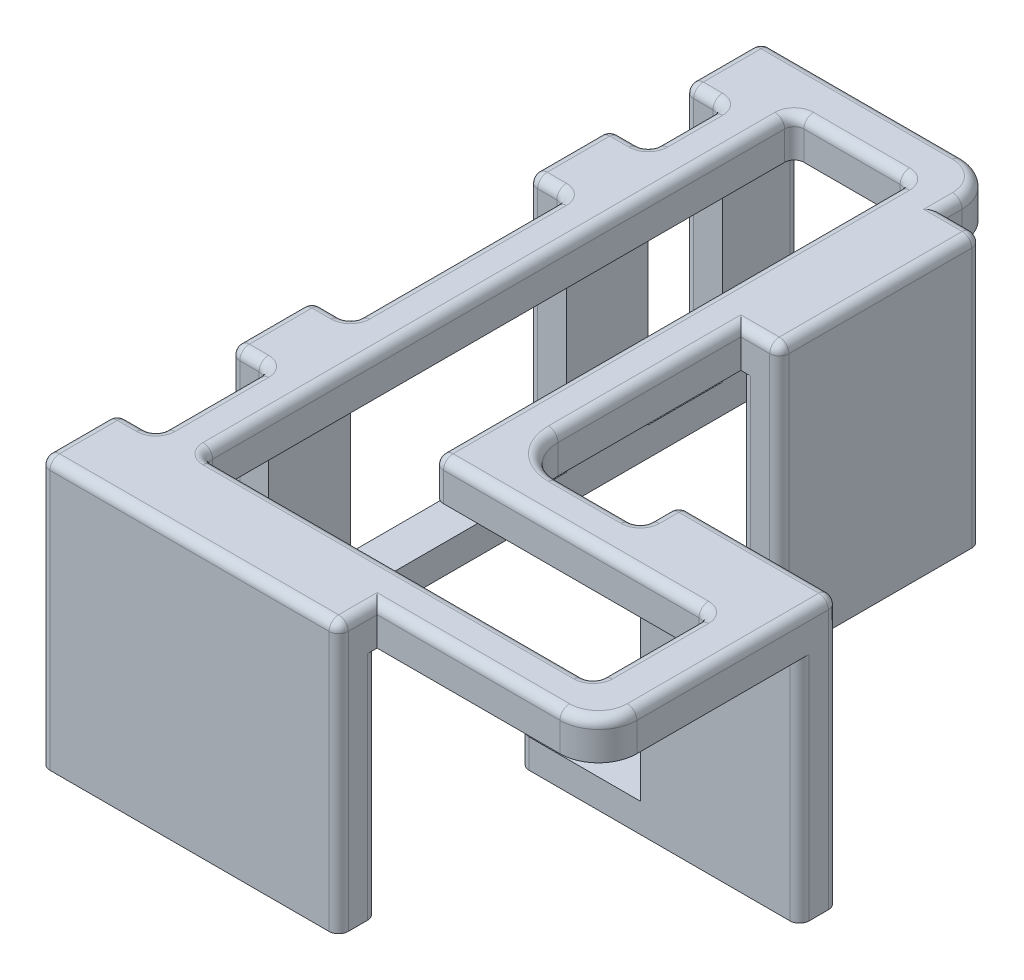
SolidWorks part; units mm, degrees
ref_plane "Front Plane" through (0, 0, 0) normal (0, 0, 1) x (1, 0, 0)
ref_plane "Top Plane" through (0, 0, 0) normal (0, 1, 0) x (1, 0, 0)
ref_plane "Right Plane" through (0, 0, 0) normal (1, 0, 0) x (0, 0, -1)
sketch "Sketch1" plane through (0, 0, 0) normal (0, 1, 0) x (1, 0, 0)
  line L5 (20.9, 20.9) -> (33.45, 20.9)
  line L6 (20.9, 43.9) -> (20.9, 20.9)
  line L18 (0, 46.675) -> (0, 35.45)
  line L23 (27, 0) -> (50, 0)
  line L27 (24.9, 43.9) -> (20.9, 43.9)
  line L30 (27, -4) -> (27, 0)
  line L42 (33.45, 24.9) -> (33.45, 20.9)
  line L43 (0, 24.225) -> (0, 35.45)
  line L51 (33.45, 24.9) -> (50, 24.9)
  line L52 (20.9, 70.9) -> (20.9, 64.9)
  line L53 (20.9, 64.9) -> (24.9, 64.9)
  line L54 (-4, 70.9) -> (20.9, 70.9)
  line L55 (24.9, 43.9) -> (24.9, 64.9)
  line L56 (-4, 51.175) -> (-4, 70.9)
  line L57 (-4, -4) -> (27, -4)
  line L58 (-4, -4) -> (-4, 19.725)
  line L59 (50, 0) -> (50, 24.9)
  line L60 (-4, 19.725) -> (-4, 24.225)
  line L61 (-4, 24.225) -> (0, 24.225)
  line L62 (-4, 51.175) -> (-4, 46.675)
  line L63 (-4, 46.675) -> (0, 46.675)
extrude "Boss-Extrude1" add sketch "Sketch1" along normal blind 4
sketch "Sketch2" plane through (0, 0, 0) normal (0, -1, 0) x (1, 0, 0)
  line L0 (27, 0) -> (23, 0)
  line L2 (23, 4) -> (27, 4)
  line L3 (27, 4) -> (27, 0)
  line L7 (33.45, -24.9) -> (33.45, -20.9)
  line L11 (24.9, -43.9) -> (20.9, -43.9)
  line L15 (-4, -15.725) -> (0, -15.725)
  line L17 (0, -55.175) -> (-4, -55.175)
  line L24 (23, 4) -> (-4, 4)
  line L25 (-4, 4) -> (-4, -4)
  line L26 (-4, -19.725) -> (-4, 4) construction
  line L27 (-4, -4) -> (0, -4)
  line L28 (0, -4) -> (0, 0)
  line L29 (0, 0) -> (23, 0)
  line L30 (33.45, -20.9) -> (50, -20.9)
  line L31 (50, 0) -> (50, -24.9) construction
  line L32 (50, -20.9) -> (50, -24.9)
  line L33 (50, -24.9) -> (33.45, -24.9)
  line L34 (-4, -70.9) -> (-4, -62.9)
  line L35 (-4, -70.9) -> (-4, -51.175) construction
  line L36 (-4, -62.9) -> (0, -62.9)
  line L37 (0, -62.9) -> (0, -70.9)
  line L38 (24.9, -70.9) -> (-4, -70.9) construction
  line L39 (0, -70.9) -> (-4, -70.9)
  line L43 (20.9, -43.9) -> (20.9, -64.9)
  line L44 (20.9, -64.9) -> (24.9, -64.9)
  line L45 (24.9, -64.9) -> (24.9, -43.9)
  line L46 (0, -15.725) -> (0, -24.225)
  line L47 (0, -24.225) -> (-4, -24.225)
  line L48 (-4, -24.225) -> (-4, -15.725)
  line L49 (0, -46.675) -> (0, -55.175)
  line L50 (0, -46.675) -> (-4, -46.675)
  line L51 (-4, -46.675) -> (-4, -55.175)
extrude "Boss-Extrude2" add sketch "Sketch2" along normal blind 24
fillet "Fillet2" radius 4 3 edges at (20.9, 2, -20.9) (20.9, 2, -70.9) (50, 2, 0)
sketch "Sketch5" plane through (0, -24, 0) normal (0, -1, 0) x (-1, 0, 0)
  line L0 (0, 19.725) -> (0, 0)
  line L1 (-27, -4) -> (4, -4)
  line L2 (-27, 0) -> (0, 0)
  line L3 (4, 51.175) -> (4, -4)
  line L4 (4, 51.175) -> (4, 70.9)
  line L7 (0, 19.725) -> (0, 70.9)
  line L8 (-27, -4) -> (-27, 0)
  line L10 (4, 70.9) -> (0, 70.9)
extrude "Boss-Extrude3" add sketch "Sketch5" against normal blind 3
sketch "Sketch7" plane through (0, -24, 0) normal (0, -1, 0) x (1, 0, 0)
  line L0 (24.9, -47.9) -> (24.9, -34.9)
  line L1 (37.45, -24.9) -> (33.45, -24.9)
  line L4 (37.45, -20.9) -> (37.45, -24.9)
  line L5 (20.9, -47.9) -> (24.9, -47.9)
  line L12 (20.9, -20.9) -> (20.9, -47.9)
  line L13 (20.9, -20.9) -> (37.45, -20.9)
  line L17 (28.9, -24.9) -> (28.9, -28.9)
  line L18 (28.9, -28.9) -> (24.9, -28.9)
  line L19 (28.9, -24.9) -> (33.45, -24.9)
  line L20 (24.9, -28.9) -> (24.9, -34.9)
  circle A0 centre (24.9, -24.9) radius 1.6
extrude "Boss-Extrude4" add sketch "Sketch7" against normal blind 3
sketch "Sketch8" plane through (0, -21, 0) normal (0, 1, 0) x (1, 0, 0)
  line L0 (0, 15.725) -> (-5, 15.725)
  line L1 (-5, 15.725) -> (-5, 10.725)
  line L2 (-5, 10.725) -> (0, 10.725)
  line L3 (0, 70.9) -> (0, 0) construction
  line L4 (0, 10.725) -> (0, 15.725)
  line L5 (0, 55.175) -> (0, 60.175)
  line L6 (0, 66.9) -> (0, 55.175) construction
  line L7 (0, 60.175) -> (-5, 60.175)
  line L8 (0, 55.175) -> (-5, 55.175)
  line L9 (-5, 55.175) -> (-5, 60.175)
extrude "Boss-Extrude5" add sketch "Sketch8" against normal blind 3
sketch "Sketch9" plane through (0, -21, 0) normal (0, 1, 0) x (1, 0, 0)
  circle A2 centre (-2.5, 57.675) radius 1.6
  circle A3 centre (-2.5, 13.225) radius 1.6
extrude "Cut-Extrude1" cut sketch "Sketch9" against normal blind 3
sketch "Sketch10" plane through (0, 4, 0) normal (0, 1, 0) x (1, 0, 0)
  line L4 (10.45, 65.9) -> (16.45, 65.9)
  line L5 (10.45, 65.9) -> (4.45, 65.9)
  line L6 (4.45, 65.9) -> (4.45, 4.45)
  line L7 (45, 10.45) -> (45, 4.45)
  line L8 (45, 4.45) -> (4.45, 4.45)
  line L9 (16.45, 65.9) -> (16.45, 16.45)
  line L10 (45, 10.45) -> (45, 16.45)
  line L11 (45, 16.45) -> (16.45, 16.45)
extrude "Cut-Extrude2" cut sketch "Sketch10" against normal blind 6
sketch "Sketch11" plane through (0, 0, 0) normal (0, -1, 0) x (-1, 0, 0)
  line L0 (0, 15.725) -> (0, 4)
  line L1 (0, 4) -> (4, 4)
  line L2 (4, 4) -> (4, 15.725)
  line L3 (4, 15.725) -> (0, 15.725)
  line L4 (0, 55.175) -> (4, 55.175)
  line L5 (4, 55.175) -> (4, 62.9)
  line L6 (4, 62.9) -> (0, 62.9)
  line L7 (0, 62.9) -> (0, 55.175)
extrude "Cut-Extrude3" cut sketch "Sketch11" against normal blind 10
fillet "Fillet3" radius 1 26 edges at (-4, -8.5, -15.725) (-4, -8.5, -55.175) (-4, -8.5, -62.9) (-4, -8.5, -4) (20.9, -10.5, -43.9) (20.9, -22.5, -20.9) (24.9, -8.5, -43.9) (33.45, 2, -20.9) (33.45, -8.5, -24.9) (50, -10, -24.9) (27, -10, 4) (-4, -10, 4) (-4, -8.5, -24.225) (0, 2, -24.225) (0, 2, -46.675) (-4, -8.5, -46.675) (-4, -10, -70.9) (24.9, -10, -64.9) (0, 2, -15.725) (0, 2, -4) (0, 2, -62.9) (0, 2, -55.175) (27, -12, 0) (50, -12, -20.9) (0, -12, -70.9) (20.9, -12, -64.9)
fillet "Fillet4" radius 1 58 edges at (22.4, 4, -43.9) (20.9, 4, -34.4) (28.675, 4, -20.9) (33.1571, 4, -21.1929) (33.45, 4, -22.9) (33.7429, 4, -24.6071) (41.725, 4, -24.9) (36.5, 4, 0) (27, 4, 1.5) (-3.7071, 4, -3.7071) (-2, 4, -4) (-0.2929, 4, -4.2929) (0, 4, -9.8625) (-0.2929, 4, -15.4321) (-2, 4, -15.725) (-3.7071, 4, -16.0179) (0, 4, -35.45) (-3.7071, 4, -54.8821) (-2, 4, -55.175) (-0.2929, 4, -55.4679) (0, 4, -59.0375) (-0.2929, 4, -62.6071) (-2, 4, -62.9) (-3.7071, 4, -63.1929) (10.45, 4, -65.9) (4.45, 4, -35.175) (30.725, 4, -16.45) (45, 4, -10.45) (24.725, 4, -4.45) (16.45, 4, -41.175) (16.45, 2, -65.9) (4.45, 2, -65.9) (4.45, 2, -4.45) (45, 2, -4.45) (45, 2, -16.45) (16.45, 2, -16.45) (20.9, 4, -65.9) (19.7284, 4, -69.7284) (-4, 4, 0) (24.9, 4, -54.4) (6.95, 4, -70.9) (11.5, 4, 4) (-3.7071, 4, -70.6071) (-3.7071, 4, 3.7071) (22.4, 4, -64.9) (24.6071, 4, -64.6071) (24.6071, 4, -44.1929) (22.0716, 4, -22.0716) (49.7071, 4, -24.6071) (50, 4, -13.95) (48.8284, 4, -1.1716) (26.7071, 4, 3.7071) (-2, 4, -46.675) (-3.7071, 4, -46.9679) (-2, 4, -24.225) (-3.7071, 4, -23.9321) (-0.2929, 4, -46.3821) (-0.2929, 4, -24.5179)
fillet "Fillet5" radius 1 4 edges at (-5, -22.5, -60.175) (-5, -22.5, -55.175) (-5, -22.5, -15.725) (-5, -22.5, -10.725)
fillet "Fillet6" radius 1 3 edges at (24.9, -22.5, -28.9) (28.9, -22.5, -28.9) (28.9, -22.5, -24.9)
